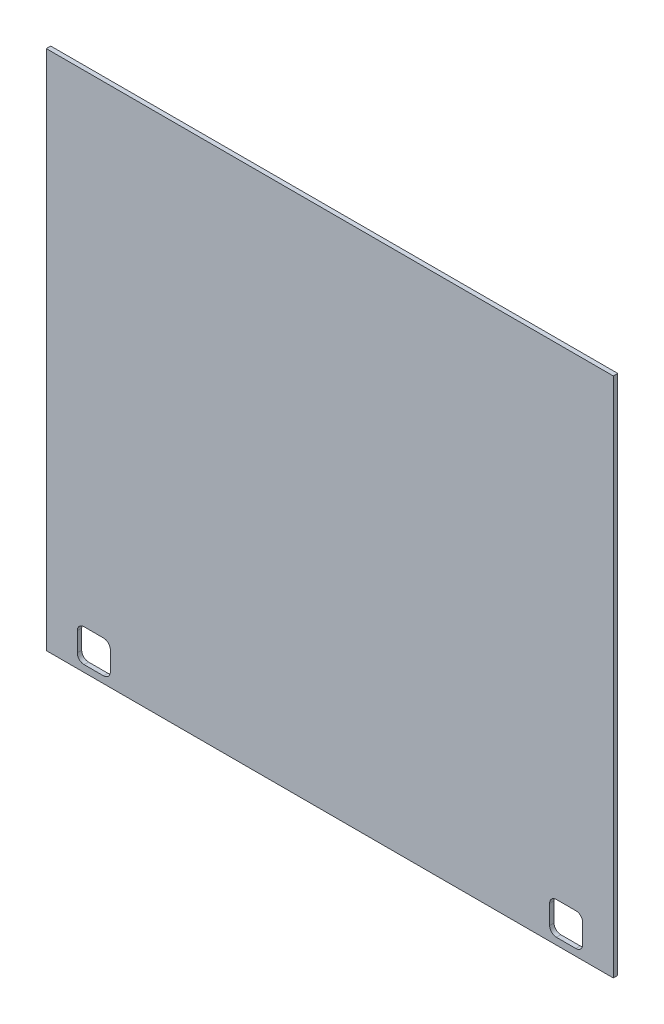
SolidWorks part; units mm, degrees
ref_plane "Plan de face" through (0, 0, 0) normal (0, 0, 1) x (1, 0, 0)
ref_plane "Plan de dessus" through (0, 0, 0) normal (0, 1, 0) x (1, 0, 0)
ref_plane "Plan de droite" through (0, 0, 0) normal (1, 0, 0) x (0, 0, -1)
sketch "Esquisse1" plane through (0, 0, 0) normal (0, 0, 1) x (1, 0, 0)
  line L1 (-416, -382.5) -> (416, -382.5)
  line L2 (-416, -382.5) -> (-416, 382.5)
  line L3 (-416, 382.5) -> (416, 382.5)
  line L4 (416, -382.5) -> (416, 382.5)
  line L5 (-416, -382.5) -> (416, 382.5) construction
  line L6 (-416, 382.5) -> (416, -382.5) construction
  point P0 (0, 0)
  dimension "D1" = 765
  dimension "D2" = 832
extrude "Boss.-Extru.1" add sketch "Esquisse1" along normal blind 6.5
sketch "Esquisse2" plane through (0, 0, 0) normal (0, 0, -1) x (-1, 0, 0)
  line L0 (416, -382.5) -> (-416, -382.5) construction
  line L1 (-361, -372.5214) -> (-332.526, -372.5214)
  line L2 (-371, -362.5214) -> (-371, -334.4752)
  line L3 (-361, -324.4752) -> (-332.526, -324.4752)
  line L4 (-322.526, -362.5214) -> (-322.526, -334.4752)
  line L5 (-371, -372.5214) -> (-322.526, -324.4752) construction
  line L6 (-371, -324.4752) -> (-322.526, -372.5214) construction
  line L7 (-416, -382.5) -> (-416, 382.5) construction
  arc A0 (-322.526, -362.5214) -> (-332.526, -372.5214) centre (-332.526, -362.5214) cw
  arc A1 (-361, -372.5214) -> (-371, -362.5214) centre (-361, -362.5214) cw
  arc A2 (-371, -334.4752) -> (-361, -324.4752) centre (-361, -334.4752) cw
  arc A3 (-322.526, -334.4752) -> (-332.526, -324.4752) centre (-332.526, -334.4752) ccw
  point P0 (-346.763, -348.4983)
  dimension "D1" = 10
  dimension "D2" = 9.9786
  dimension "D3" = 45
  dimension "D4" = 28.0461
extrude "Enlèv. mat.-Extru.1" cut sketch "Esquisse2" against normal through all
ref_axis "Axe1" through (0, 382.5, 0) along (0, -1, 0)
pattern_linear "Répétition linéaire1" count 2 spacing 693 along (-1, 0, 0) of "Enlèv. mat.-Extru.1"
